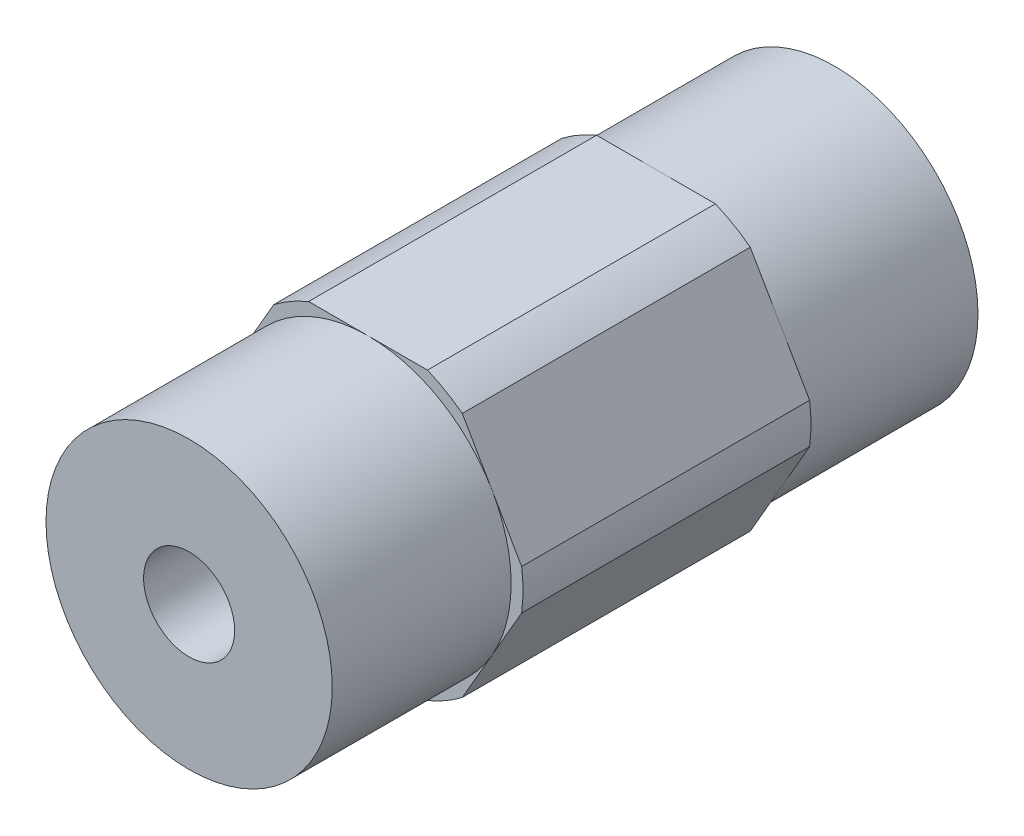
SolidWorks part; units mm, degrees
material "7075-T6 (SN)"
ref_plane "Front Plane" through (0, 0, 0) normal (0, 0, 1) x (1, 0, 0)
ref_plane "Top Plane" through (0, 0, 0) normal (0, 1, 0) x (1, 0, 0)
ref_plane "Right Plane" through (0, 0, 0) normal (1, 0, 0) x (0, 0, -1)
sketch "Sketch1" plane through (0, 0, 0) normal (0, 0, 1) x (1, 0, 0)
  line L1 (7.3323, 0) -> (3.6662, 6.35)
  line L2 (3.6662, 6.35) -> (-3.6662, 6.35)
  line L3 (-3.6662, 6.35) -> (-7.3323, 0)
  line L4 (-7.3323, 0) -> (-3.6662, -6.35)
  line L5 (-3.6662, -6.35) -> (3.6662, -6.35)
  line L6 (3.6662, -6.35) -> (7.3323, 0)
  circle A0 centre (0, 0) radius 6.35 construction
  circle A1 centre (0, 0) radius 2.0193
  circle A2 centre (0, 0) radius 6.875
  dimension "D1" = 12.7
  dimension "D2" = 4.0386
  dimension "D3" = 13.75
extrude "Boss-Extrude1" add sketch "Sketch1" along normal mid plane 28.6512 contours L1 A2 L2 L3 L4 L5 L6 A1 region at (6.6736, 0.4353, 0)
hole_wizard "#10-32 Tapped Hole1" positions "3DSketch1" profile "Sketch3" tap size "#10-32" standard "ANSI Inch"
sketch3d "3DSketch1"
  circle A0 centre (0, 0, -14.3256) radius 2.0193 construction
  circle A1 centre (0, 0, 14.3256) radius 2.0193 construction
  point P0 (0, 0, 14.3256)
  point P2 (0, 0, -14.3256)
  point P6 (0, 0, -12.3063)
  point P9 (0, 0, 16.3449)
sketch "Sketch3" plane through (0, 0, 14.3256) normal (1, 0, 0) x (0, -1, 0)
  line L0 (0, 0) -> (0, 13.1513)
  line L1 (0, 13.1513) -> (2.0193, 11.938)
  line L2 (2.0193, 11.938) -> (2.0193, 0)
  line L5 (2.0193, 0) -> (0, 0)
  line L10 (0, 13.1513) -> (-2.0193, 11.938) construction
  line L11 (0, -6.35) -> (0, 107.95) construction
  dimension "Tap Drill Dia." = 4.0386
  dimension "Tap Drill Depth" = 11.938
  dimension "Drill Angle" = 118
cosmetic thread "Hole Thread1" parameters "D1"=9.652, "D2"=4.826
cosmetic thread "Hole Thread2" parameters "D1"=9.652, "D2"=4.826
sketch "Sketch4" plane through (0, 0, 14.3256) normal (0, 0, 1) x (1, 0, 0)
  circle A0 centre (0, 0) radius 6.35
  dimension "D1" = 12.7
extrude "Cut-Extrude-Thin1" cut sketch "Sketch4" against normal blind 7.9375 thin thin type one direction wall 2.54
mirror "Mirror1" about plane through (0, 0, 0) normal (0, 0, 1) of "Cut-Extrude-Thin1"
equation "\"D3@Sketch1\"=13.75mm"
